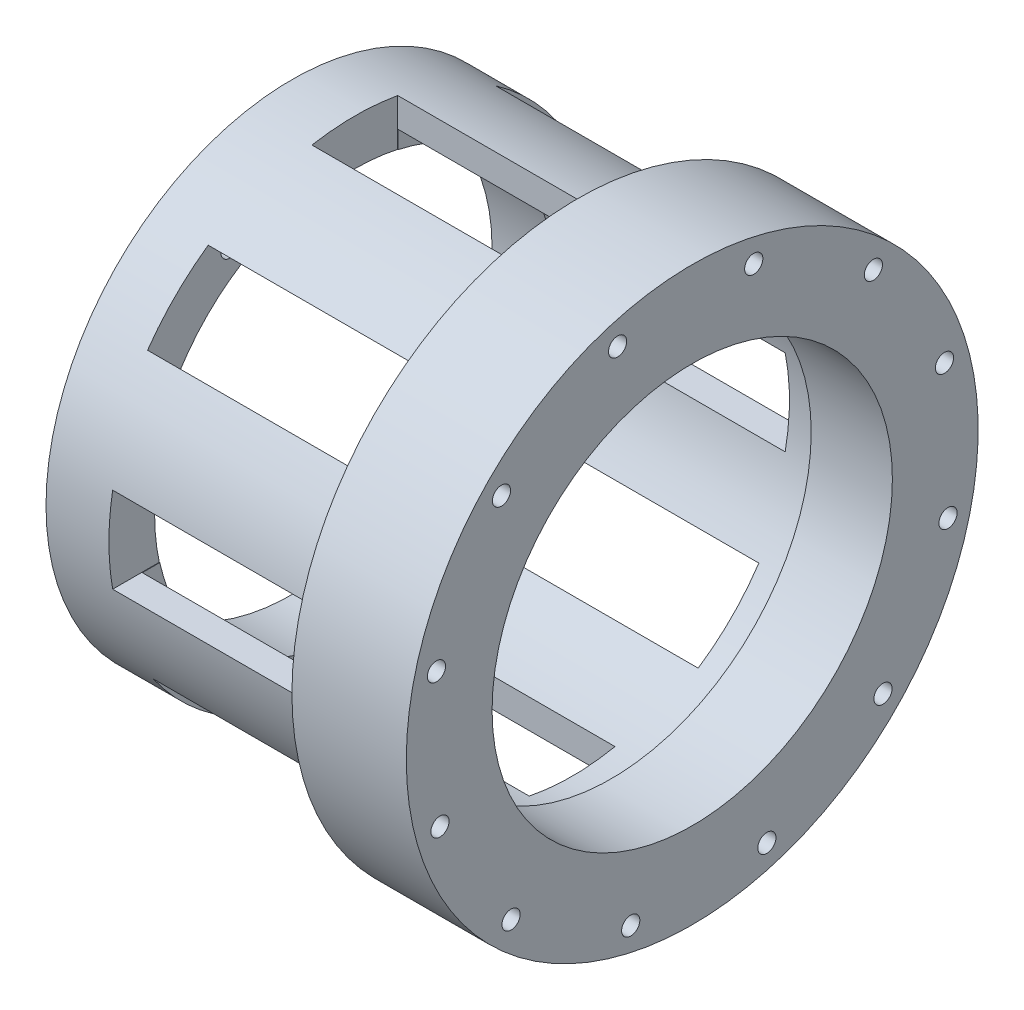
SolidWorks part; units mm, degrees
material "6061 Alloy"
ref_plane "Front Plane" through (0, 0, 0) normal (0, 0, 1) x (1, 0, 0)
ref_plane "Top Plane" through (0, 0, 0) normal (0, 1, 0) x (1, 0, 0)
ref_plane "Right Plane" through (0, 0, 0) normal (1, 0, 0) x (0, 0, -1)
sketch "Sketch1" plane through (0, 0, 0) normal (0, 0, 1) x (1, 0, 0)
  line L0 (-87.2836, 0) -> (119.6109, 0) construction
  line L1 (-88.9, 54.61) -> (-88.9, 44.45)
  line L2 (-88.9, 44.45) -> (0, 44.45)
  line L3 (0, 44.45) -> (0, 63.5)
  line L4 (0, 63.5) -> (-25.4, 63.5)
  line L5 (-25.4, 63.5) -> (-25.4, 54.61)
  line L6 (-25.4, 54.61) -> (-88.9, 54.61)
  dimension "D1" = 88.9
  dimension "D2" = 88.9
  dimension "D3" = 19.05
  dimension "D4" = 10.16
  dimension "D5" = 25.4
revolve "Revolve1" add sketch "Sketch1" angle 360 about L0
sketch "Sketch4" plane through (0, 0, 0) normal (1, 0, 0) x (0, 0, -1)
  circle A4 centre (56.0204, 16.5715) radius 2.0193 construction
  circle A5 centre (56.8008, -13.6589) radius 2.0193 construction
  circle A6 centre (42.3615, -40.2293) radius 2.0193 construction
  circle A7 centre (16.5715, -56.0204) radius 2.0193 construction
  circle A8 centre (-13.6589, -56.8008) radius 2.0193 construction
  circle A9 centre (-40.2293, -42.3615) radius 2.0193 construction
  circle A14 centre (-56.0204, -16.5715) radius 2.0193 construction
  circle A15 centre (-56.8008, 13.6589) radius 2.0193 construction
  circle A16 centre (40.2293, 42.3615) radius 2.0193 construction
  circle A17 centre (13.6589, 56.8008) radius 2.0193 construction
  circle A18 centre (-16.5715, 56.0204) radius 2.0193 construction
  circle A19 centre (-42.3615, 40.2293) radius 2.0193 construction
  circle A24 centre (56.0204, 16.5715) radius 2.0193
  circle A25 centre (56.8008, -13.6589) radius 2.0193
  circle A26 centre (42.3615, -40.2293) radius 2.0193
  circle A27 centre (16.5715, -56.0204) radius 2.0193
  circle A28 centre (-13.6589, -56.8008) radius 2.0193
  circle A29 centre (-40.2293, -42.3615) radius 2.0193
  circle A34 centre (-56.0204, -16.5715) radius 2.0193
  circle A35 centre (-56.8008, 13.6589) radius 2.0193
  circle A36 centre (40.2293, 42.3615) radius 2.0193
  circle A37 centre (13.6589, 56.8008) radius 2.0193
  circle A38 centre (-16.5715, 56.0204) radius 2.0193
  circle A39 centre (-42.3615, 40.2293) radius 2.0193
extrude "Upper Bolt Holes " cut sketch "Sketch4" against normal up to next
sketch "Sketch6" plane through (-88.9, 0, 0) normal (-1, 0, 0) x (0, 0, 1)
  circle A0 centre (0, 0) radius 49.53 construction
  circle A1 centre (-10.9052, 48.3146) radius 2.0193
  circle A2 centre (-13.6589, 56.8008) radius 2.0193 construction
  circle A3 centre (26.4524, 41.8747) radius 2.0193
  circle A4 centre (48.3146, 10.9052) radius 2.0193
  circle A5 centre (41.8747, -26.4524) radius 2.0193
  circle A6 centre (10.9052, -48.3146) radius 2.0193
  circle A7 centre (-26.4524, -41.8747) radius 2.0193
  circle A8 centre (-48.3146, -10.9052) radius 2.0193
  circle A9 centre (-41.8747, 26.4524) radius 2.0193
  dimension "D1" = 99.06
  dimension "D2" = 8
extrude "Lower Bolt Holes " cut sketch "Sketch6" against normal blind 12.7
sketch "Sketch7" plane through (0, 0, 0) normal (0, 0, 1) x (1, 0, 0)
  line L0 (0, 44.45) -> (-88.9, 44.45) construction
  line L1 (-74.8231, 44.45) -> (-18.0279, 44.45)
  line L2 (-74.8231, 44.45) -> (-74.8231, 48.26)
  line L3 (-74.8231, 48.26) -> (-18.0279, 48.26)
  line L4 (-18.0279, 44.45) -> (-18.0279, 48.26)
  line L5 (-102.6686, 0) -> (27.0314, 0) construction
  dimension "D1" = 3.81
revolve "0.15in Depth Air Gap" cut sketch "Sketch7" angle 360 about L5
sketch "Sketch8" plane through (0, 0, 0) normal (0, 1, 0) x (1, 0, 0)
  line L0 (-25.4, 63.5) -> (-25.4, -63.5) construction
  line L1 (-26.67, -9.525) -> (-74.93, -9.525)
  line L2 (-26.67, -9.525) -> (-26.67, 9.525)
  line L3 (-26.67, 9.525) -> (-74.93, 9.525)
  line L4 (-74.93, -9.525) -> (-74.93, 9.525)
  line L5 (-26.67, -9.525) -> (-74.93, 9.525) construction
  line L6 (-26.67, 9.525) -> (-74.93, -9.525) construction
  line L7 (-114.2997, 0) -> (25.2319, 0) construction
  point P0 (-50.8, 0)
  dimension "D1" = 48.26
  dimension "D2" = 19.05
  dimension "D3" = 1.27
extrude "SideWall Cutout 1" cut sketch "Sketch8" against normal mid plane 152.4
sketch "Sketch10" plane through (0, 0, 0) normal (0, 0, 1) x (1, 0, 0)
  line L0 (-103.5935, 0) -> (33.1684, 0) construction
  line L1 (-25.4, 63.5) -> (-25.4, -63.5) construction
  line L2 (-74.93, -9.525) -> (-26.67, -9.525)
  line L3 (-74.93, -9.525) -> (-74.93, 9.525)
  line L4 (-74.93, 9.525) -> (-26.67, 9.525)
  line L5 (-26.67, -9.525) -> (-26.67, 9.525)
  line L6 (-74.93, -9.525) -> (-26.67, 9.525) construction
  line L7 (-74.93, 9.525) -> (-26.67, -9.525) construction
  point P2 (-50.8, 0)
  dimension "D1" = 48.26
  dimension "D2" = 19.05
  dimension "D3" = 1.27
extrude "SideWall Cutout 2" cut sketch "Sketch10" against normal mid plane 152.4
ref_axis "Axis1" through (4.445, 0, 0) along (-1, 0, 0)
ref_plane "Plane1" through (0, 0, 0) normal (0, 0.7071, 0.7071) x (-1, 0, 0)
ref_plane "Plane2" through (0, 0, 0) normal (0, -0.7071, 0.7071) x (-1, 0, 0)
sketch "Sketch11" plane through (0, 0, 0) normal (0, 0.7071, 0.7071) x (-1, 0, 0)
  line L0 (50.8, 44.7584) -> (50.8, -65.2822) construction
  line L1 (26.67, 44.7584) -> (74.93, 44.7584) construction
  line L2 (-23.0257, 0) -> (162.3464, 0) construction
  line L4 (25.4, -9.525) -> (76.2, -9.525)
  line L5 (25.4, -9.525) -> (25.4, 9.525)
  line L6 (25.4, 9.525) -> (76.2, 9.525)
  line L7 (76.2, -9.525) -> (76.2, 9.525)
  line L8 (25.4, -9.525) -> (76.2, 9.525) construction
  line L9 (25.4, 9.525) -> (76.2, -9.525) construction
  point P7 (50.8, 0)
  dimension "D1" = 19.05
extrude "SideWall Cutout 3" cut sketch "Sketch11" against normal mid plane 152.4
sketch "Sketch13" plane through (0, 0, 0) normal (0, -0.7071, 0.7071) x (-1, 0, 0)
  line L0 (-42.5129, 0) -> (158.449, 0) construction
  line L1 (50.8, 44.7584) -> (50.8, -94.513) construction
  line L2 (26.67, 44.7584) -> (74.93, 44.7584) construction
  line L4 (26.67, -9.525) -> (74.93, -9.525)
  line L5 (26.67, -9.525) -> (26.67, 9.525)
  line L6 (26.67, 9.525) -> (74.93, 9.525)
  line L7 (74.93, -9.525) -> (74.93, 9.525)
  line L8 (26.67, -9.525) -> (74.93, 9.525) construction
  line L9 (26.67, 9.525) -> (74.93, -9.525) construction
  point P7 (50.8, 0)
  dimension "D1" = 19.05
extrude "SideWall Cutout 4" cut sketch "Sketch13" against normal mid plane 152.4
